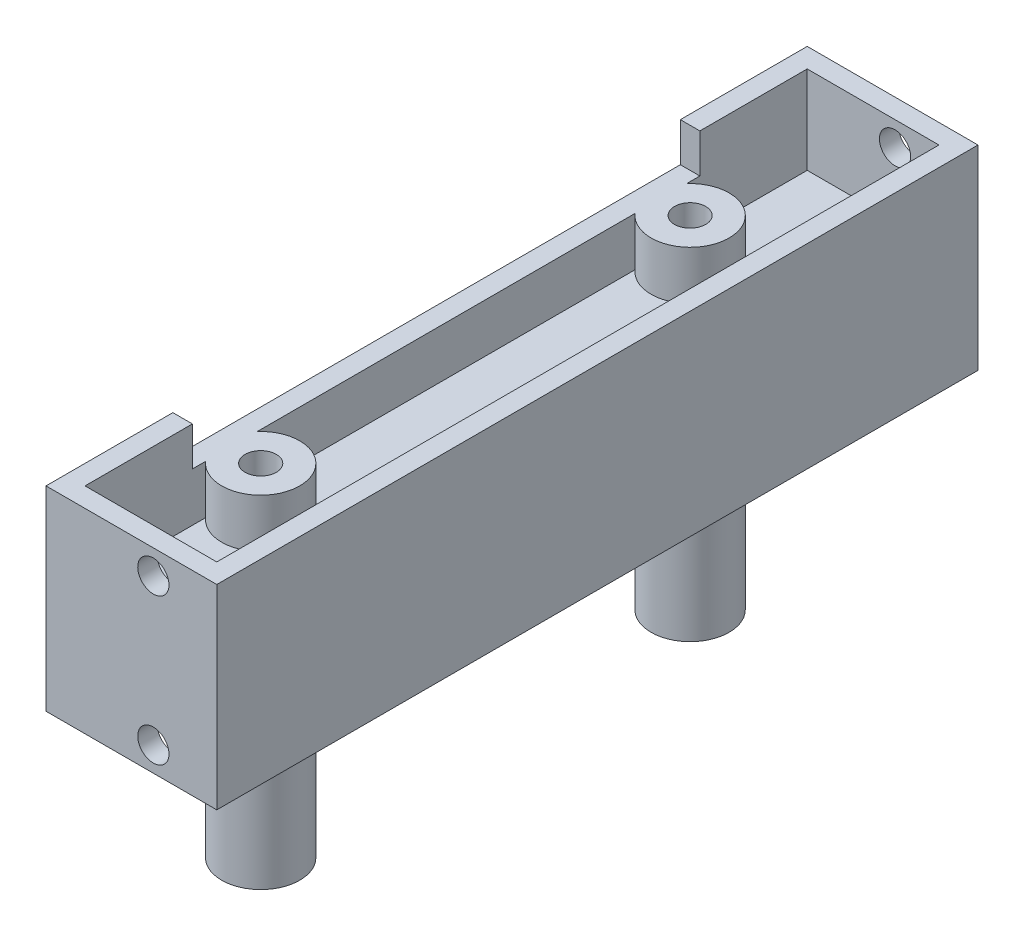
SolidWorks part; units mm, degrees
material "PET"
ref_plane "前视基准面" through (0, 0, 0) normal (0, 0, 1) x (1, 0, 0)
ref_plane "上视基准面" through (0, 0, 0) normal (0, 1, 0) x (1, 0, 0)
ref_plane "右视基准面" through (0, 0, 0) normal (1, 0, 0) x (0, 0, -1)
other "Configuration Table"
sketch "草图1" plane through (0, 0, 0) normal (0, 1, 0) x (1, 0, 0)
  line L1 (-30, -39) -> (30, -39)
  line L2 (-30, -39) -> (-30, 39)
  line L3 (-30, 39) -> (30, 39)
  line L4 (30, -39) -> (30, 39)
  line L5 (-30, -39) -> (30, 39) construction
  line L6 (-30, 39) -> (30, -39) construction
  point P0 (0, 0)
  dimension "D1" = 60
  dimension "D2" = 78
extrude "凸台-拉伸1" add sketch "草图1" along normal blind 2
sketch "草图2" plane through (0, 2, 0) normal (0, 1, 0) x (1, 0, 0)
  line L0 (-30, 0) -> (30, 0) construction
  line L1 (-30, 39) -> (-30, -39) construction
  line L2 (30, -39) -> (30, 39) construction
  line L3 (-24.5, 0) -> (-24.5, 22) construction
  circle A0 centre (-24.5, 22) radius 1.6
  circle A1 centre (19.5, 22) radius 1.6
  circle A2 centre (19.5, -22) radius 1.6
  circle A3 centre (-24.5, -22) radius 1.6
  dimension "D3" = 3.2
  dimension "D4" = 44
  dimension "D5" = 22
  dimension "D6" = 3.2
  dimension "D1" = 22
  dimension "D2" = 5.5
extrude "切除-拉伸1" cut sketch "草图2" against normal blind 12
sketch "草图3" plane through (0, 0, 39) normal (0, 0, 1) x (1, 0, 0)
  line L0 (-30, 2) -> (30, 0) construction
  line L1 (30, 2) -> (-30, 0) construction
  line L3 (-30, -9) -> (30, -9)
  line L4 (-30, -9) -> (-30, 11)
  line L5 (-30, 11) -> (30, 11)
  line L6 (30, -9) -> (30, 11)
  line L7 (-30, -9) -> (30, 11) construction
  line L8 (-30, 11) -> (30, -9) construction
  point P8 (0, 1)
  dimension "D1" = 20
extrude "凸台-拉伸2" add sketch "草图3" against normal blind 2
ref_plane "基准面1" through (0, 0, 0) normal (0, 0, 1) x (1, 0, 0)
mirror "镜向1" about plane through (0, 0, 0) normal (0, 0, 1) of "凸台-拉伸2"
sketch "草图4" plane through (0, 0, 39) normal (0, 0, 1) x (1, 0, 0)
  line L0 (-30, 1) -> (30, 1) construction
  line L1 (-30, 11) -> (-30, -9) construction
  line L2 (30, 11) -> (30, -9) construction
  line L3 (-25.5, 1) -> (-25.5, 8.5) construction
  line L4 (0, 11) -> (0, -9) construction
  line L5 (30, 11) -> (-30, 11) construction
  line L6 (-30, -9) -> (30, -9) construction
  circle A0 centre (-25.5, 8.5) radius 1.6
  circle A1 centre (-25.5, -6.5) radius 1.6
  circle A2 centre (25.5, -6.5) radius 1.6
  circle A3 centre (25.5, 8.5) radius 1.6
  dimension "D1" = 3.2
  dimension "D3" = 25.5
  dimension "D2" = 7.5
extrude "切除-拉伸2" cut sketch "草图4" against normal blind 126
sketch "草图5" plane through (0, 2, 0) normal (0, 1, 0) x (1, 0, 0)
  line L0 (0, 37) -> (0, -37) construction
  line L1 (30, 37) -> (-30, 37) construction
  line L2 (30, -37) -> (-30, -37) construction
  line L6 (-8.525, 0) -> (8.525, 0) construction
  circle A1 centre (-22.5, 32) radius 1.9469
  circle A2 centre (-7.5, 32) radius 1.9469
  circle A3 centre (7.5, 32) radius 1.9469
  circle A4 centre (22.5, 32) radius 1.9469
  circle A5 centre (22.5, -32) radius 1.9469
  circle A6 centre (7.5, -32) radius 1.9469
  circle A7 centre (-7.5, -32) radius 1.9469
  circle A8 centre (-22.5, -32) radius 1.9469
  dimension "D1" = 32
  dimension "D2" = 22.5
  dimension "D3" = 4
sketch "草图6" plane through (0, 2, 0) normal (0, 1, 0) x (1, 0, 0)
  circle A0 centre (-24.5, 22) radius 4
  circle A1 centre (19.5, 22) radius 4
  circle A2 centre (-24.5, -22) radius 4
  circle A3 centre (19.5, -22) radius 4
  circle A4 centre (-24.5, 22) radius 1.6
  circle A5 centre (19.5, 22) radius 1.6
  circle A6 centre (-24.5, -22) radius 1.6
  circle A8 centre (19.5, -22) radius 1.6
  dimension "D1" = 8
  dimension "D2" = 8
  dimension "D3" = 8
  dimension "D4" = 8
  dimension "D5" = 3.2
  dimension "D6" = 3.2
  dimension "D7" = 3.2
  dimension "D8" = 3.2
extrude "凸台-拉伸3" add sketch "草图6" against normal blind 30 and the other way blind 5
fillet "圆角1" radius 2 2 edges at (0, 0, 37) (0, 0, -37)
sketch "草图7" plane through (0, 0, -39) normal (0, 0, -1) x (-1, 0, 0)
  line L0 (0, 11) -> (0, 9) construction
  line L1 (-30, 11) -> (30, 11) construction
  circle A0 centre (0, 9) radius 1.5
  dimension "D2" = 3
  dimension "D1" = 2
extrude "切除-拉伸4" cut sketch "草图7" against normal blind 81
sketch "草图8" plane through (0, 0, -39) normal (0, 0, -1) x (-1, 0, 0)
  line L0 (30, -9) -> (-30, -9) construction
  circle A0 centre (0, -9) radius 2.5
  dimension "D1" = 5
extrude "切除-拉伸5" cut sketch "草图8" against normal blind 113
sketch "草图9" plane through (0, 2, 0) normal (0, 1, 0) x (1, 0, 0)
  circle A0 centre (-24.5, -22) radius 3
  circle A1 centre (19.5, -22) radius 3
  circle A2 centre (-24.5, 22) radius 3
  circle A3 centre (19.5, 22) radius 3
  dimension "D1" = 6
  dimension "D2" = 6
  dimension "D3" = 6
  dimension "D4" = 6
sketch "草图10" plane through (0, 0, 0) normal (0, -1, 0) x (-1, 0, 0)
  line L0 (-11, 0) -> (11, 0) construction
  line L1 (33.2702, 23.1872) -> (-14.7787, 23.1872)
  line L2 (33.2702, 23.1872) -> (33.2702, -23.1872)
  line L3 (33.2702, -23.1872) -> (-14.7787, -23.1872)
  line L4 (-14.7787, 23.1872) -> (-14.7787, -23.1872)
  line L5 (33.2702, 23.1872) -> (-14.7787, -23.1872) construction
  line L6 (33.2702, -23.1872) -> (-14.7787, 23.1872) construction
  point P0 (9.2458, 0)
sketch "草图11" plane through (0, 2, 0) normal (0, 1, 0) x (1, 0, 0)
  line L0 (-24.5, 22) -> (19.5, -22) construction
  line L1 (19.5, 22) -> (-24.5, -22) construction
  line L3 (-18.5, -16) -> (13.5, -16)
  line L4 (-18.5, -16) -> (-18.5, 16)
  line L5 (-18.5, 16) -> (13.5, 16)
  line L6 (13.5, -16) -> (13.5, 16)
  line L7 (-18.5, -16) -> (13.5, 16) construction
  line L8 (-18.5, 16) -> (13.5, -16) construction
  point P8 (-2.5, 0)
  dimension "D1" = 32
extrude "切除-拉伸6" cut sketch "草图11" against normal blind 10
fillet "圆角2" radius 5 4 edges at (13.5, 1, 16) (-18.5, 1, 16) (-18.5, 1, -16) (13.5, 1, -16)
sketch "草图12" plane through (0, 0, 0) normal (0, -1, 0) x (-1, 0, 0)
  line L0 (30, -39) -> (-14.5, -39)
  line L1 (-2.5, -39) -> (-30, -39) construction
  line L2 (-14.5, -39) -> (-14.5, 39)
  line L3 (-2.5, 39) -> (-30, 39) construction
  line L4 (-14.5, 39) -> (30, 39)
  line L5 (30, -39) -> (30, 39)
  circle A0 centre (-19.5, -22) radius 4 construction
  dimension "D1" = 5
extrude "切除-拉伸7" cut sketch "草图12" against normal blind 47 and the other way blind 73
sketch "草图13" plane through (14.5, 0, 0) normal (-1, 0, 0) x (0, 0, 1)
  line L0 (-37, 2) -> (37, 2) construction
  line L1 (37, -9) -> (37, -2) construction
  line L2 (37, 2) -> (37, 11) construction
  line L3 (-37, -2) -> (-37, -9) construction
  line L4 (35, 0) -> (-35, 0) construction
  line L5 (-37, 11) -> (-37, 2) construction
  line L6 (-37, 2) -> (37, 2)
  line L7 (37, -9) -> (37, -2)
  line L8 (37, 2) -> (37, 11)
  line L9 (-37, -2) -> (-37, -9)
  line L10 (35, 0) -> (-35, 0)
  line L11 (-37, 11) -> (-37, 2)
  line L12 (-37, 11) -> (37, 11)
  line L13 (-37, -9) -> (37, -9)
  arc A0 (37, -2) -> (35, 0) centre (35, -2) ccw construction
  arc A1 (-35, 0) -> (-37, -2) centre (-35, -2) ccw construction
  arc A2 (37, -2) -> (35, 0) centre (35, -2) ccw
  arc A3 (-35, 0) -> (-37, -2) centre (-35, -2) ccw
extrude "凸台-拉伸4" add sketch "草图13" against normal blind 2
ref_plane "基准面2" through (22.25, 0, 0) normal (-1, 0, 0) x (0, 0, 1)
sketch "草图14" plane through (30, 0, 0) normal (1, 0, 0) x (0, 0, -1)
  line L1 (-39, 11) -> (39, 11)
  line L2 (-39, 11) -> (-39, -9)
  line L3 (-39, -9) -> (39, -9)
  line L4 (39, 11) -> (39, -9)
extrude "凸台-拉伸5" add sketch "草图14" along normal blind 2
sketch "草图16" plane through (0, 11, 0) normal (0, 1, 0) x (1, 0, 0)
  line L0 (14.7787, 23.1872) -> (14.7787, -23.1872) construction
  line L1 (10.0574, -26) -> (19.5, -26)
  line L2 (10.0574, -26) -> (10.0574, 26)
  line L3 (10.0574, 26) -> (19.5, 26)
  line L4 (19.5, -26) -> (19.5, 26)
  line L5 (10.0574, -26) -> (19.5, 26) construction
  line L6 (10.0574, 26) -> (19.5, -26) construction
  arc A0 (16.5, 19.3542) -> (16.5, 24.6458) centre (19.5, 22) ccw construction
  point P0 (14.7787, 0)
extrude "切除-拉伸8" cut sketch "草图16" against normal up to surface (4 mm away) up to face at (19.5, 7, -20.4)
